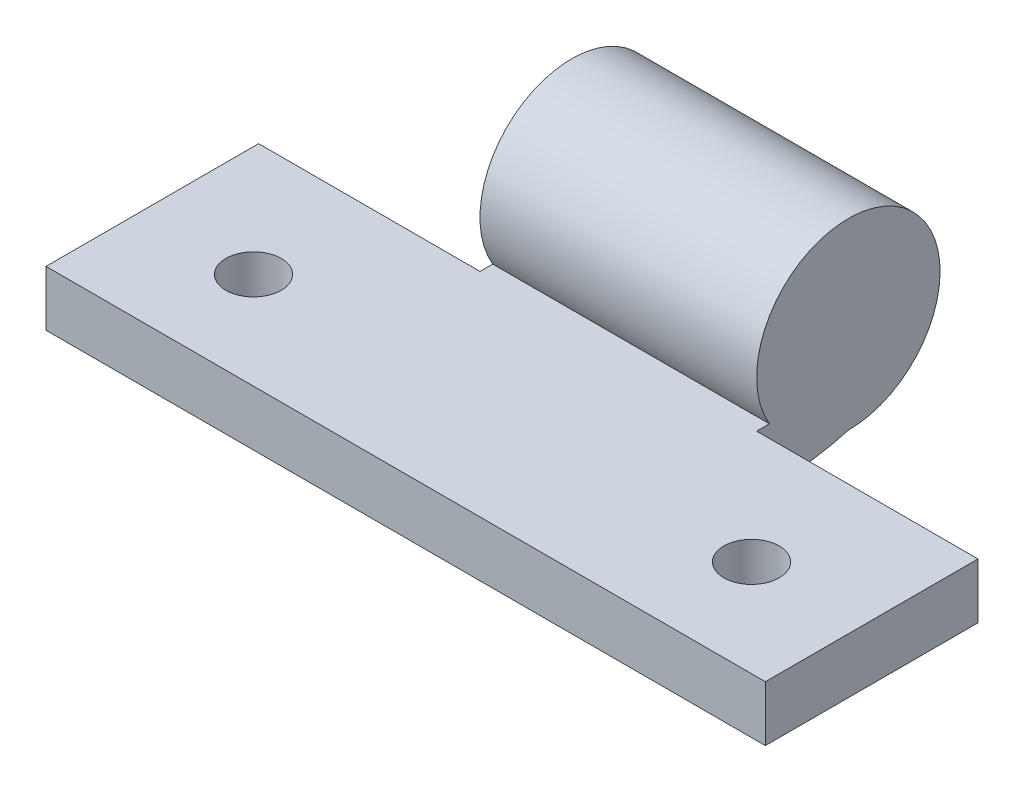
SolidWorks part; units mm, degrees
material "ABS"
ref_plane "前视基准面" through (0, 0, 0) normal (0, 0, 1) x (1, 0, 0)
ref_plane "上视基准面" through (0, 0, 0) normal (0, 1, 0) x (1, 0, 0)
ref_plane "右视基准面" through (0, 0, 0) normal (1, 0, 0) x (0, 0, -1)
sketch "草图1" plane through (0, 0, 0) normal (0, 1, 0) x (1, 0, 0)
  line L0 (0, 0) -> (0, -7.5) construction
  line L1 (-22.1376, 0) -> (22.1376, 0) construction
  line L2 (-13, -11) -> (13, -11)
  line L3 (13, -11) -> (13, 0)
  line L4 (13, 0) -> (-13, 0)
  line L5 (-9, -7.5) -> (9, -7.5) construction
  line L6 (-13, -11) -> (-13, 0)
  circle A0 centre (9, -7.5) radius 1
  circle A1 centre (-9, -7.5) radius 1
  point P14 (0, -11)
  dimension "D5" = 2
  dimension "D1" = 13
  dimension "D2" = 22
  dimension "D3" = 7.5
  dimension "D4" = 9
extrude "凸台-拉伸1" add sketch "草图1" along normal blind 2
sketch "草图2" plane through (13, 0, 0) normal (1, 0, 0) x (0, 0, -1)
  line L0 (0, 0) -> (0, 7) construction
  circle A0 centre (0, 3.685) radius 3.315
  dimension "D2" = 6.63
  dimension "D1" = 7
extrude "凸台-拉伸2" add sketch "草图2" against normal up to surface (26 mm away) up to face at (-13, 1, 5.5)
fillet "圆角1" radius 10 1 edges at (0, 0, 0)
sketch "草图3" plane through (0, 2, 0) normal (0, 1, 0) x (1, 0, 0)
  line L0 (-5, 0) -> (5, 0) construction
  line L1 (5, -3.315) -> (5, 3.315)
  line L2 (-13, -3.315) -> (13, -3.315) construction
  line L3 (13, 3.315) -> (-13, 3.315) construction
  line L4 (5, 3.315) -> (13, 3.315)
  line L5 (13, 3.315) -> (13, -3.315)
  line L6 (13, -3.315) -> (5, -3.315)
  line L7 (0, 0) -> (0, 6.9942) construction
  line L8 (-13, -3.315) -> (-5, -3.315)
  line L9 (-13, 3.315) -> (-13, -3.315)
  line L10 (-5, 3.315) -> (-13, 3.315)
  line L11 (-5, -3.315) -> (-5, 3.315)
  dimension "D1" = 5
extrude "切除-拉伸1" cut sketch "草图3" against normal through all both and the other way through all
